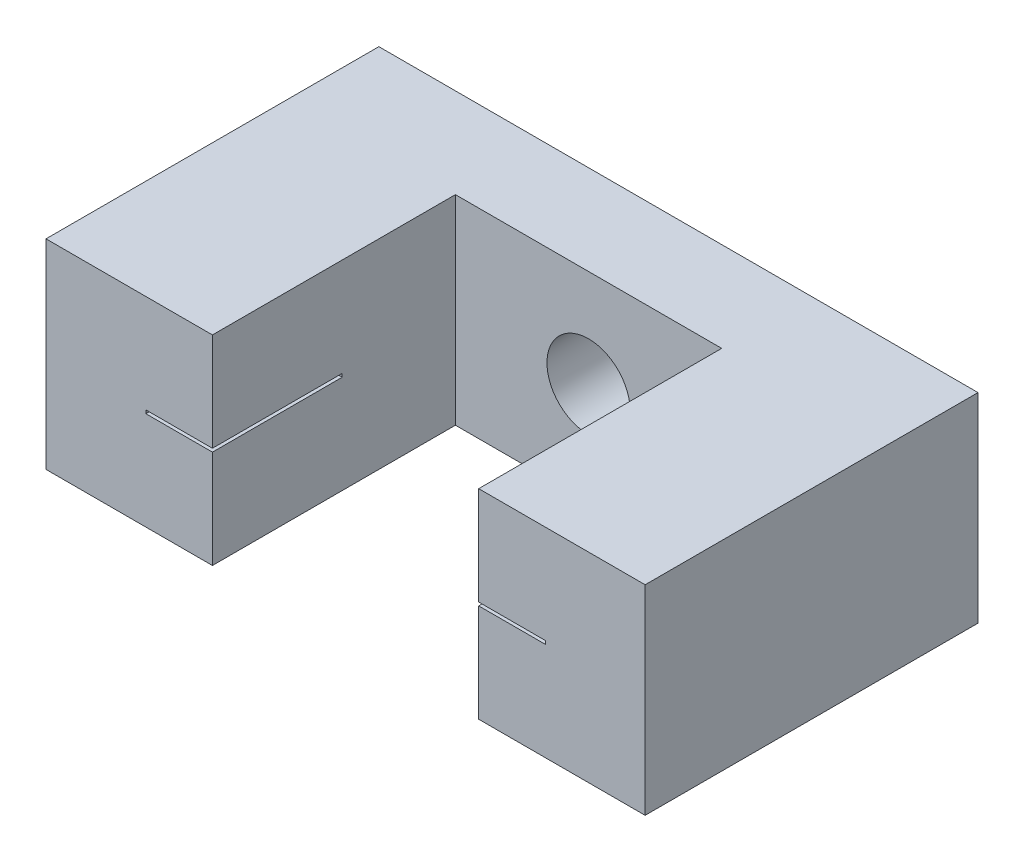
SolidWorks part; units mm, degrees
ref_plane "Front Plane" through (0, 0, 0) normal (0, 0, 1) x (1, 0, 0)
ref_plane "Top Plane" through (0, 0, 0) normal (0, 1, 0) x (1, 0, 0)
ref_plane "Right Plane" through (0, 0, 0) normal (1, 0, 0) x (0, 0, -1)
sketch "Sketch2" plane through (0, 0, 0) normal (0, 1, 0) x (1, 0, 0)
  line L0 (0, 0) -> (18, 0)
  line L1 (18, 0) -> (18, -10)
  line L2 (18, -10) -> (13, -10)
  line L3 (13, -10) -> (13, -2.7)
  line L4 (13, -2.7) -> (5, -2.7)
  line L5 (5, -2.7) -> (5, -10)
  line L6 (5, -10) -> (0, -10)
  line L7 (0, -10) -> (0, 0)
  dimension "D1" = 18
  dimension "D2" = 10
  dimension "D3" = 0
  dimension "D4" = 8
  dimension "D5" = 5
  dimension "D6" = 5
  dimension "D7" = 7.3
extrude "Boss-Extrude1" add sketch "Sketch2" along normal blind 6 contours L0 L1 L2 L3 L4 L5 L6 L7
sketch "Sketch3" plane through (0, 0, 2.7) normal (0, 0, 1) x (1, 0, 0)
  line L0 (13, 6) -> (5, 6) construction
  line L1 (5, 6) -> (5, 0) construction
  circle A0 centre (9, 3) radius 1.25
  dimension "D1" = 2.5
  dimension "D2" = 3
  dimension "D3" = 4
extrude "Cut-Extrude1" cut sketch "Sketch3" against normal up to surface (2.7 mm away) up to face at (9, 3, 0)
sketch "Sketch4" plane through (5, 0, 0) normal (1, 0, 0) x (0, 0, -1)
  line L0 (-10, 6) -> (-10, 0) construction
  line L1 (-10, 3.05) -> (-6.1, 3.05)
  line L2 (-10, 3.05) -> (-10, 2.95)
  line L3 (-10, 2.95) -> (-6.1, 2.95)
  line L4 (-6.1, 3.05) -> (-6.1, 2.95)
  line L5 (-2.7, 6) -> (-10, 6) construction
  line L6 (-2.7, 0) -> (-10, 0) construction
  point P6 (-6.1, 3)
  dimension "D1" = 3.9
  dimension "D2" = 0.1
  dimension "D3" = 2.95
  dimension "D4" = 2.95
extrude "Cut-Extrude2" cut sketch "Sketch4" against normal blind 2 contours L1 L4 L3 L2
ref_axis "Axis1" through (9, 3, 0) along (0, 0, 1)
ref_plane "Plane1" through (9, 0, 0) normal (1, 0, 0) x (0, 0, -1)
mirror "Mirror1" about plane through (9, 0, 0) normal (1, 0, 0) of "Cut-Extrude2"
sketch "Sketch5" plane through (0, 0, 0) normal (0, 0, -1) x (-1, 0, 0)
  line L0 (0, 6) -> (0, 0) construction
  line L1 (-3.5, 4) -> (-1.5, 4)
  line L2 (-3.5, 4) -> (-3.5, 2)
  line L3 (-3.5, 2) -> (-1.5, 2)
  line L4 (-1.5, 4) -> (-1.5, 2)
  line L5 (0, 6) -> (-18, 6) construction
  dimension "D1" = 2
  dimension "D2" = 2
  dimension "D3" = 1.5
  dimension "D4" = 2
extrude "Cut-Extrude3" cut sketch "Sketch5" against normal blind 8
mirror "Mirror2" about plane through (9, 0, 0) normal (1, 0, 0) of "Cut-Extrude3"
